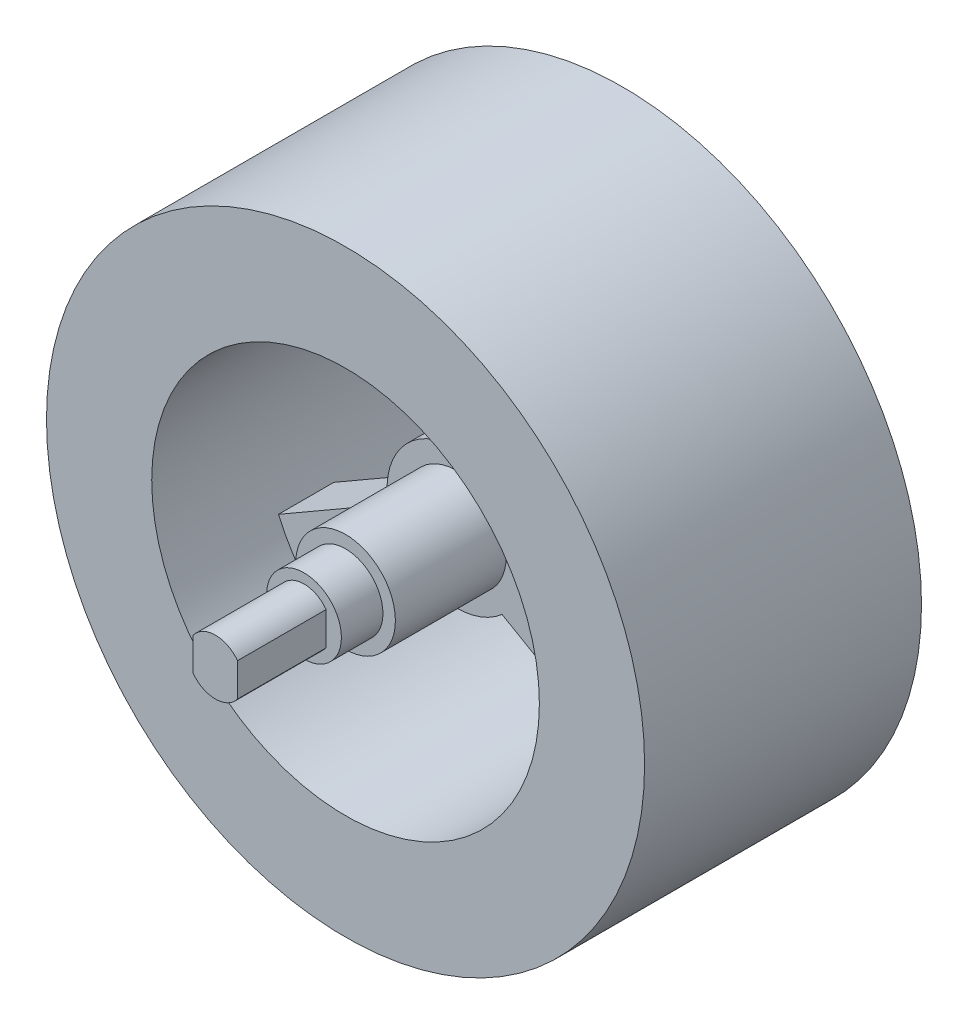
SolidWorks part; units mm, degrees
ref_plane "Front Plane" through (0, 0, 0) normal (0, 0, 1) x (1, 0, 0)
ref_plane "Top Plane" through (0, 0, 0) normal (0, 1, 0) x (1, 0, 0)
ref_plane "Right Plane" through (0, 0, 0) normal (1, 0, 0) x (0, 0, -1)
sketch "Sketch1" plane through (0, 0, 0) normal (0, 0, 1) x (1, 0, 0)
  circle A0 centre (0, 0) radius 6.75
  dimension "D1" = 13.5
extrude "Boss-Extrude1" add sketch "Sketch1" along normal mid plane 65 contours A0
sketch "Sketch3" plane through (0, 0, 0) normal (0, 0, 1) x (1, 0, 0)
  circle A0 centre (0, 0) radius 5
  dimension "D1" = 10
extrude "Boss-Extrude3" add sketch "Sketch3" along normal mid plane 97
sketch "Sketch4" plane through (0, 0, 0) normal (0, 0, 1) x (1, 0, 0)
  circle A0 centre (0, 0) radius 54
  circle A1 centre (0, 0) radius 35
  dimension "D1" = 108
  dimension "D2" = 70
extrude "Boss-Extrude4" add sketch "Sketch4" along normal mid plane 50
sketch "Sketch5" plane through (0, 0, 0) normal (0, 0, 1) x (1, 0, 0)
  line L0 (12.2561, -2.4573) -> (8.2561, -9.3855)
  line L1 (-4, 11.8427) -> (4, 11.8427)
  line L2 (-4, 11.8427) -> (-4, 35)
  line L3 (-4, 35) -> (4, 35)
  line L4 (4, 11.8427) -> (4, 35)
  line L5 (12.2561, -2.4573) -> (32.3109, -14.0359)
  line L6 (32.3109, -14.0359) -> (28.3109, -20.9641)
  line L7 (8.2561, -9.3855) -> (28.3109, -20.9641)
  line L8 (-8.2561, -9.3855) -> (-12.2561, -2.4573)
  line L9 (-8.2561, -9.3855) -> (-28.3109, -20.9641)
  line L10 (-28.3109, -20.9641) -> (-32.3109, -14.0359)
  line L11 (-12.2561, -2.4573) -> (-32.3109, -14.0359)
  line L12 (0, 0) -> (4, 11.8427) construction
  circle A0 centre (0, 0) radius 12.5
  circle A1 centre (0, 0) radius 35 construction
  dimension "D1" = 25
  dimension "D2" = 8
  dimension "D3" = 3
extrude "Boss-Extrude5" add sketch "Sketch5" along normal mid plane 10 contours L1 A0 L8 L0 | A0 L4 L3 L2 | A0 L7 L6 L5 | A0 L11 L10 L9 | L8 A0 | L0 A0 | L1 A0 | L2 L1 L4 L3 region at (10.4843, -6.0531, 0) region at (20.4735, -11.8204, 0) region at (0, 0, 0) region at (-10.4843, -6.0531, 0) region at (-20.4735, -11.8204, 0) region at (0, 23.6408, 0) region at (0, 12.1062, 0)
sketch "Sketch6" plane through (0, 0, 0) normal (0, 0, 1) x (1, 0, 0)
  circle A0 centre (0, 0) radius 9
  dimension "D1" = 18
extrude "Boss-Extrude6" add sketch "Sketch6" along normal mid plane 50
sketch "Sketch7" plane through (0, 0, -48.5) normal (0, 0, -1) x (-1, 0, 0)
  line L1 (4, 3) -> (5, 3)
  line L2 (4, 3) -> (4, -3)
  line L3 (4, -3) -> (5, -3)
  line L4 (5, 3) -> (5, -3)
  line L5 (-4, 3) -> (-5, 3)
  line L6 (-4, 3) -> (-4, -3)
  line L7 (-4, -3) -> (-5, -3)
  line L8 (-5, 3) -> (-5, -3)
  circle A0 centre (0, 0) radius 5 construction
  circle A1 centre (0, 0) radius 5 construction
  point P4 (0, 0)
  dimension "D1" = 8
extrude "Cut-Extrude1" cut sketch "Sketch7" against normal blind 16
mirror "Mirror1" about plane through (0, 0, 0) normal (0, 0, 1) of "Cut-Extrude1"
sketch "Sketch8" plane through (0, 0, -48.5) normal (0, 0, -1) x (-1, 0, 0)
  circle A0 centre (0, 0) radius 3
  dimension "D1" = 6
extrude "Cut-Extrude2" cut sketch "Sketch8" against normal up to surface (48.5 mm away) up to plane "Front Plane"
